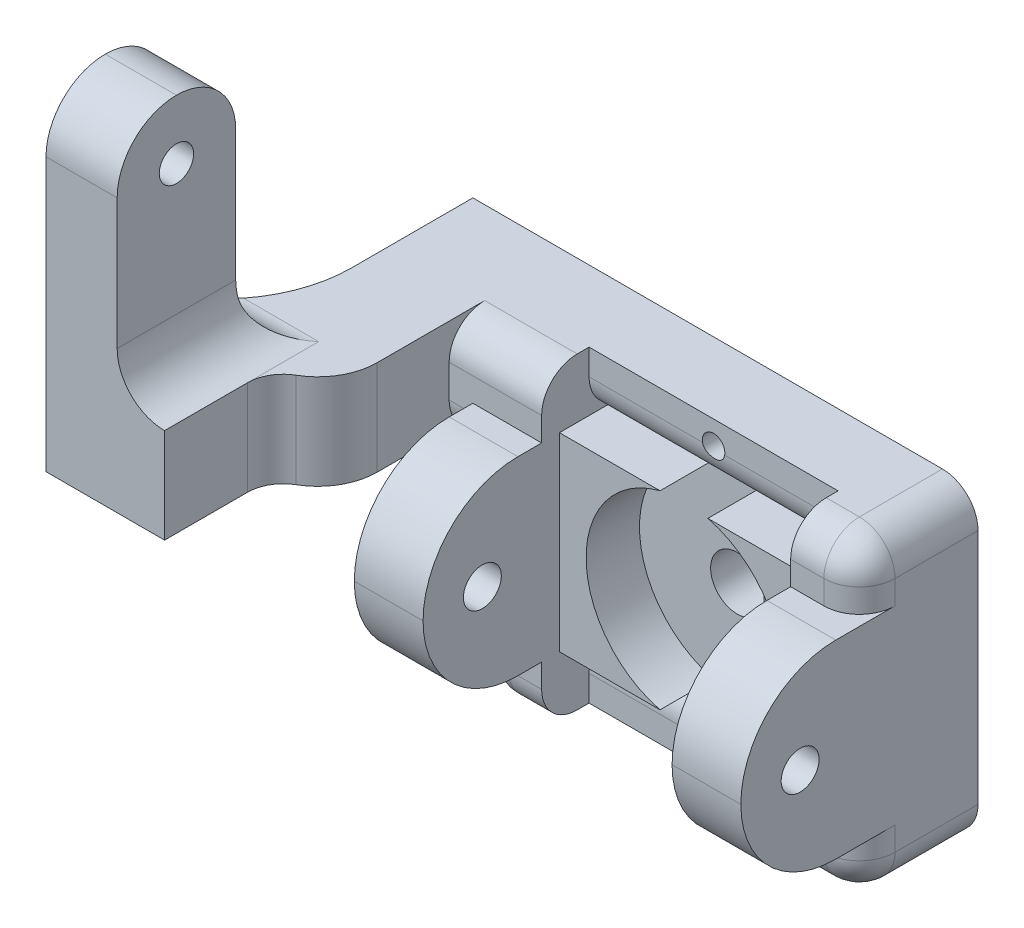
SolidWorks part; units mm, degrees
ref_plane "Front" through (0, 0, 0) normal (0, 0, 1) x (1, 0, 0)
ref_plane "Top" through (0, 0, 0) normal (0, 1, 0) x (1, 0, 0)
ref_plane "Right" through (0, 0, 0) normal (1, 0, 0) x (0, 0, -1)
sketch "Sketch1" plane through (0, 0, 0) normal (0, 0, 1) x (1, 0, 0)
  line L1 (0, 0) -> (-32.6, 0)
  line L2 (0, 0) -> (0, 26)
  line L3 (0, 26) -> (-32.6, 26)
  line L4 (-32.6, 0) -> (-32.6, 26)
  dimension "D1" = 32.6
  dimension "D2" = 26
extrude "Boss-Extrude1" add sketch "Sketch1" along normal blind 4
sketch "Sketch2" plane through (0, 0, 4) normal (0, 0, 1) x (1, 0, 0)
  line L0 (0, 26) -> (-32.6, 26) construction
  line L1 (0, 0) -> (0, 26) construction
  circle A0 centre (-16.3, 13) radius 2.25
  dimension "D1" = 4.5
  dimension "D2" = 13
  dimension "D3" = 16.3
extrude "Cut-Extrude1" cut sketch "Sketch2" against normal blind 2.5
sketch "Sketch3" plane through (0, 0, 1.5) normal (0, 0, 1) x (1, 0, 0)
  circle A0 centre (-16.3, 13) radius 2.25
  dimension "D1" = 4.5
extrude "Cut-Extrude2" cut sketch "Sketch3" against normal through all
sketch "Sketch4" plane through (0, 0, 4) normal (0, 0, 1) x (1, 0, 0)
  line L0 (-32.6, 0) -> (0, 0) construction
  line L1 (0, 26) -> (-5.8, 26)
  line L2 (0, 26) -> (0, 0)
  line L3 (0, 0) -> (-5.8, 0)
  line L4 (-5.8, 26) -> (-5.8, 0)
  line L6 (-32.6, 26) -> (-26.8, 26)
  line L7 (-32.6, 26) -> (-32.6, 0)
  line L8 (-32.6, 0) -> (-26.8, 0)
  line L9 (-26.8, 26) -> (-26.8, 0)
  dimension "D1" = 5.8
  dimension "D2" = 5.8
extrude "Boss-Extrude2" add sketch "Sketch4" along normal blind 16
sketch "Sketch5" plane through (0, 0, 0) normal (1, 0, 0) x (0, 0, -1)
  line L0 (-20, 0) -> (-20, 26) construction
  line L1 (-20, 0) -> (0, 0) construction
  circle A0 centre (-15, 13) radius 1.6
  dimension "D1" = 3.2
  dimension "D2" = 5
  dimension "D3" = 13
extrude "Cut-Extrude3" cut sketch "Sketch5" against normal through all
sketch "Sketch6" plane through (0, 0, 4) normal (0, 0, 1) x (1, 0, 0)
  line L1 (-26.8, 26) -> (-5.8, 26)
  line L2 (-26.8, 26) -> (-26.8, 21)
  line L3 (-26.8, 21) -> (-5.8, 21)
  line L4 (-5.8, 26) -> (-5.8, 21)
  line L5 (-26.8, 0) -> (-5.8, 0)
  line L6 (-26.8, 0) -> (-26.8, 5)
  line L7 (-26.8, 5) -> (-5.8, 5)
  line L8 (-5.8, 0) -> (-5.8, 5)
  dimension "D1" = 5
  dimension "D2" = 5
extrude "Boss-Extrude3" add sketch "Sketch6" along normal blind 2
sketch "Sketch7" plane through (-32.6, 0, 0) normal (-1, 0, 0) x (0, 0, 1)
  line L1 (20, 26) -> (10, 26)
  line L2 (20, 26) -> (20, 21)
  line L3 (20, 21) -> (10, 21)
  line L4 (10, 26) -> (10, 21)
  line L5 (20, 0) -> (10, 0)
  line L6 (20, 0) -> (20, 5)
  line L7 (20, 5) -> (10, 5)
  line L8 (10, 0) -> (10, 5)
  dimension "D1" = 10
  dimension "D2" = 10
  dimension "D3" = 5
  dimension "D4" = 5
extrude "Cut-Extrude4" cut sketch "Sketch7" against normal through all
fillet "Fillet1" radius 8 4 edges at (-2.9, 5, 20) (-2.9, 21, 20) (-29.7, 5, 20) (-29.7, 21, 20)
sketch "Sketch12" plane through (-32.6, 0, 0) normal (-1, 0, 0) x (0, 0, 1)
  line L0 (0, 26) -> (0, 0) construction
  line L1 (10, 26) -> (0, 26)
  line L2 (10, 26) -> (10, 18)
  line L3 (10, 18) -> (0, 18)
  line L4 (0, 26) -> (0, 18)
  dimension "D1" = 8
extrude "Boss-Extrude8" add sketch "Sketch12" along normal blind 10
sketch "Sketch13" plane through (0, 0, 10) normal (0, 0, 1) x (1, 0, 0)
  line L0 (-26.8, 26) -> (-42.6, 26) construction
  line L1 (-42.6, 18) -> (-34.6, 18)
  line L2 (-42.6, 18) -> (-42.6, 26)
  line L3 (-42.6, 26) -> (-34.6, 26)
  line L4 (-34.6, 18) -> (-34.6, 26)
  dimension "D1" = 8
extrude "Boss-Extrude9" add sketch "Sketch13" along normal blind 10
fillet "Fillet2" radius 3 4 edges at (-30.7, 26, 10) (-2.9, 26, 10) (-2.9, 0, 10) (-29.7, 0, 10)
sketch "Sketch14" plane through (0, 0, 20) normal (0, 0, 1) x (1, 0, 0)
  line L0 (-42.6, 18) -> (-34.6, 18) construction
  line L1 (-38.6, 18) -> (-48.6, 18)
  line L2 (-38.6, 18) -> (-38.6, 26)
  line L3 (-38.6, 26) -> (-48.6, 26)
  line L4 (-48.6, 18) -> (-48.6, 26)
  dimension "D1" = 8
  dimension "D2" = 10
extrude "Boss-Extrude10" add sketch "Sketch14" along normal blind 10
sketch "Sketch15" plane through (0, 26, 0) normal (0, 1, 0) x (1, 0, 0)
  line L1 (-48.6, -30) -> (-42.6, -30)
  line L2 (-48.6, -30) -> (-48.6, -20)
  line L3 (-48.6, -20) -> (-42.6, -20)
  line L4 (-42.6, -30) -> (-42.6, -20)
  dimension "D1" = 10
  dimension "D2" = 6
extrude "Boss-Extrude11" add sketch "Sketch15" along normal blind 20
fillet "Fillet10" radius 11 1 edges at (-42.6, 22, 20)
fillet "Fillet11" radius 3 1 edges at (-38.6, 22, 20)
fillet "Fillet12" radius 5 1 edges at (-34.6, 22, 20)
fillet "Fillet14" radius 4 1 edges at (-42.6, 26, 25)
fillet "Fillet15" radius 3 1 edges at (-43.6, 26, 20)
sketch "Sketch16" plane through (0, 0, 0) normal (0, 0, -1) x (-1, 0, 0)
  line L0 (42.6, 18) -> (32.6, 18)
  line L1 (32.6, 18) -> (32.6, 9)
  line L2 (32.6, 18) -> (32.6, 0) construction
  line L3 (32.6, 9) -> (42.6, 18)
  dimension "D1" = 9
extrude "Boss-Extrude12" add sketch "Sketch16" against normal blind 9
fillet "Fillet17" radius 3 1 edges at (-32.6, 9, 4.5)
fillet "Fillet18" radius 3 1 edges at (-33.6, 18, 10)
sketch "Sketch17" plane through (-48.6, 0, 0) normal (-1, 0, 0) x (0, 0, 1)
  line L0 (30, 46) -> (30, 18) construction
  line L1 (20, 46) -> (30, 46) construction
  circle A0 centre (25, 41) radius 1.45
  dimension "D1" = 2.9
  dimension "D2" = 5
  dimension "D3" = 5
extrude "Cut-Extrude5" cut sketch "Sketch17" against normal through all
fillet "Fillet19" radius 5 2 edges at (-45.6, 46, 20) (-45.6, 46, 30)
fillet "Fillet21" radius 3 2 edges at (-16.3, 21, 6) (-16.3, 5, 6)
fillet "Fillet22" radius 3 9 edges at (0, 22, 10) (0, 25.1213, 9.1213) (0, 4, 10) (0, 0.8787, 9.1213) (-32.6, 4, 10) (-32.6, 0.8787, 9.1213) (0, 26, 3.5) (0, 0, 3.5) (-32.6, 0, 3.5)
sketch "Sketch18" plane through (0, 0, 0) normal (0, 0, -1) x (-1, 0, 0)
  line L0 (29.6, 0) -> (3, 0) construction
  line L1 (3, 26) -> (42.6, 26) construction
  line L2 (0, 3) -> (0, 23) construction
  line L3 (32.6, 7.6639) -> (32.6, 3) construction
  circle A0 centre (16.3, 2) radius 0.95
  circle A1 centre (3.5, 13) radius 1.2
  circle A2 centre (29.1, 13) radius 1.2
  circle A3 centre (16.3, 24) radius 0.95
  dimension "D1" = 1.9
  dimension "D2" = 1.9
  dimension "D3" = 2.4
  dimension "D4" = 2.4
  dimension "D5" = 2
  dimension "D6" = 2
  dimension "D7" = 3.5
  dimension "D8" = 3.5
  dimension "D9" = 13
extrude "Cut-Extrude6" cut sketch "Sketch18" against normal blind 8
sketch "Sketch19" plane through (0, 0, 4) normal (0, 0, 1) x (1, 0, 0)
  line L1 (-5.8, 21) -> (-26.8, 21)
  line L2 (-5.8, 21) -> (-5.8, 5)
  line L3 (-5.8, 5) -> (-26.8, 5)
  line L4 (-26.8, 21) -> (-26.8, 5)
  circle A0 centre (-16.3, 13) radius 8.25
  line M2 (-26.8, 21) -> (-26.8, 5)
  line M3 (-26.8, 5) -> (-5.8, 5)
  line M4 (-5.8, 5) -> (-5.8, 21)
  line M5 (-5.8, 21) -> (-26.8, 21)
  dimension "D1" = 16.5
extrude "Boss-Extrude13" add sketch "Sketch19" along normal blind 4.5 contours A0 M3 M4 M5 | A0 M5 M2 M3 region at (-5.9811, 13, 4) region at (-24.7311, 13, 4)
